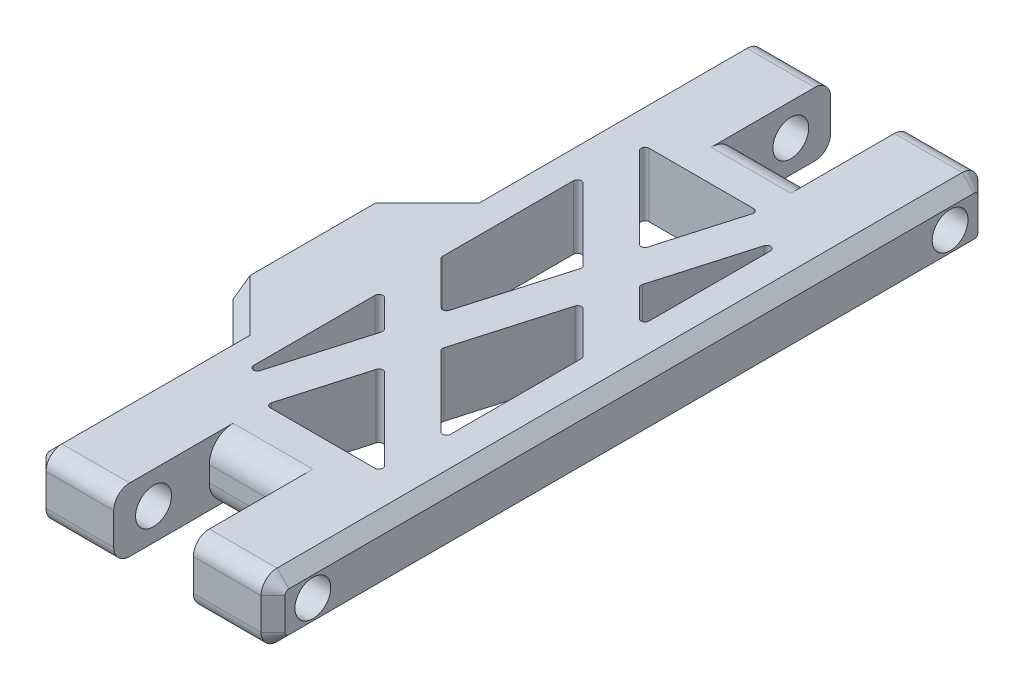
SolidWorks part; units mm, degrees
ref_plane "Front Plane" through (0, 0, 0) normal (0, 0, 1) x (1, 0, 0)
ref_plane "Top Plane" through (0, 0, 0) normal (0, 1, 0) x (1, 0, 0)
ref_plane "Right Plane" through (0, 0, 0) normal (1, 0, 0) x (0, 0, -1)
sketch "Sketch1" plane through (0, 0, 0) normal (0, 1, 0) x (1, 0, 0)
  line L1 (-15, 45) -> (15, 45)
  line L2 (-15, 45) -> (-15, -45)
  line L3 (-15, -45) -> (15, -45)
  line L4 (15, 45) -> (15, -45)
  line L5 (-15, 45) -> (15, -45) construction
  line L6 (-15, -45) -> (15, 45) construction
  point P0 (0, 0)
  dimension "D1" = 30
  dimension "D2" = 90
extrude "Boss-Extrude1" add sketch "Sketch1" along normal blind 8
sketch "Sketch2" plane through (0, 8, 0) normal (0, 1, 0) x (1, 0, 0)
  line L0 (15, 45) -> (-15, 45) construction
  line L1 (-5, 45) -> (5, 45)
  line L2 (-5, 45) -> (-5, 33)
  line L3 (-5, 33) -> (5, 33)
  line L4 (5, 45) -> (5, 33)
  line L5 (-15, -45) -> (15, -45) construction
  line L6 (5, -45) -> (-5, -45)
  line L7 (5, -45) -> (5, -33)
  line L8 (5, -33) -> (-5, -33)
  line L9 (-5, -45) -> (-5, -33)
  line L10 (15, -45) -> (15, 45) construction
  dimension "D1" = 10
  dimension "D2" = 10
  dimension "D3" = 10
  dimension "D4" = 12
  dimension "D5" = 12
  dimension "D6" = 10
extrude "Cut-Extrude1" cut sketch "Sketch2" against normal blind 8
sketch "Sketch3" plane through (15, 0, 0) normal (1, 0, 0) x (0, 0, -1)
  line L0 (-45, 8) -> (-45, 0) construction
  line L1 (-45, 8) -> (45, 8) construction
  circle A0 centre (-40, 4) radius 2.25
  dimension "D1" = 4.5
  dimension "D2" = 5
  dimension "D3" = 4
extrude "Cut-Extrude2" cut sketch "Sketch3" against normal through all
mirror "Mirror1" about plane through (0, 0, 0) normal (0, 0, 1) of "Cut-Extrude2"
fillet "Fillet1" radius 2 8 edges at (10, 0, -45) (10, 8, -45) (-10, 8, -45) (-10, 0, -45) (-10, 8, 45) (-10, 0, 45) (10, 0, 45) (10, 8, 45)
sketch "Sketch4" plane through (0, 8, 0) normal (0, 1, 0) x (1, 0, 0)
  line L0 (5, 26) -> (-10, 26)
  line L1 (-10, 26) -> (1.6418, 14.3582)
  line L2 (10, 6) -> (10, 26)
  line L3 (-10, -6) -> (-10, -26)
  line L4 (-5, -26) -> (10, -26)
  line L5 (10, -26) -> (-1.6418, -14.3582)
  line L6 (15, -43) -> (15, 43) construction
  line L7 (-15, 43) -> (-15, -43) construction
  line L8 (-10, 18.9289) -> (-10, 1.0711)
  line L9 (-10, 1.0711) -> (-3.9393, -4.9896)
  line L10 (9.8408, -18.7697) -> (9.8408, -0.9118)
  line L11 (9.8408, -0.9118) -> (3.9393, 4.9896)
  line L12 (-5, 33) -> (5, 33) construction
  line L13 (5, -33) -> (-5, -33) construction
  line L14 (5, 26) -> (1.6418, 14.3582)
  line L15 (-5, -26) -> (-1.6418, -14.3582)
  line L16 (-0.0587, -8.8702) -> (3.9393, 4.9896)
  line L18 (5.5224, 10.4776) -> (10, 6)
  line L19 (0.0587, 8.8702) -> (-10, 18.9289)
  line L20 (-0.0587, -8.8702) -> (9.8408, -18.7697)
  line L21 (-5.5224, -10.4776) -> (-10, -6)
  line L22 (-5.5224, -10.4776) -> (-10, -26)
  line L23 (0.0587, 8.8702) -> (-3.9393, -4.9896)
  line L24 (5.5224, 10.4776) -> (10, 26)
  dimension "D1" = 5
  dimension "D2" = 5
  dimension "D3" = 5
  dimension "D4" = 45
  dimension "D5" = 45
  dimension "D6" = 5
  dimension "D7" = 5
  dimension "D8" = 7
  dimension "D9" = 7
  dimension "D10" = 20
  dimension "D11" = 20
  dimension "D12" = 15
  dimension "D13" = 14
extrude "Cut-Extrude3" cut sketch "Sketch4" against normal through all
fillet "Fillet2" radius 3 4 edges at (0, 8, -33) (0, 8, 33) (0, 0, 33) (0, 0, -33)
sketch "Sketch5" plane through (-15, 0, 0) normal (-1, 0, 0) x (0, 0, 1)
  line L0 (-43, 0) -> (43, 0) construction
  line L1 (15, 0) -> (-5, 0)
  line L2 (15, 0) -> (15, 8)
  line L3 (15, 8) -> (-5, 8)
  line L4 (-5, 0) -> (-5, 8)
  line L5 (-43, 8) -> (43, 8) construction
  line L6 (-45, 6) -> (-45, 2) construction
  dimension "D1" = 40
  dimension "D2" = 20
extrude "Boss-Extrude2" add sketch "Sketch5" along normal blind 5
sketch "Sketch6" plane through (-20, 0, 0) normal (-1, 0, 0) x (0, 0, 1)
  line L0 (-5, 0) -> (15, 0) construction
  line L1 (-5, 8) -> (-5, 0) construction
  circle A0 centre (5, 4) radius 2
  dimension "D1" = 4
  dimension "D2" = 4
  dimension "D3" = 10
extrude "Cut-Extrude4" cut sketch "Sketch6" against normal blind 5
chamfer "Chamfer1" distance 5 angle 45 2 edges at (-15, 4, 15) (-15, 4, -5)
chamfer "Chamfer2" distance 1.5 angle 45 18 edges at (-15, 0, -26.5) (-15, 0.5858, -44.4142) (-15, 4, -45) (-15, 7.4142, -44.4142) (-15, 8, -26.5) (-15, 0, 31.5) (-15, 0.5858, 44.4142) (-15, 4, 45) (-15, 7.4142, 44.4142) (-15, 8, 31.5) (15, 0, 0) (15, 0.5858, 44.4142) (15, 0.5858, -44.4142) (15, 4, 45) (15, 4, -45) (15, 7.4142, 44.4142) (15, 7.4142, -44.4142) (15, 8, 0)
fillet "Fillet4" radius 0.5 20 edges at (10, 4, 26) (-1.6418, 4, 14.3582) (-5, 4, 26) (-5.5224, 4, 10.4776) (-10, 4, 6) (-10, 4, 26) (9.8408, 4, 18.7697) (9.8408, 4, 0.9118) (3.9393, 4, -4.9896) (-0.0587, 4, 8.8702) (-3.9393, 4, 4.9896) (-10, 4, -1.0711) (0.0587, 4, -8.8702) (-10, 4, -18.9289) (-10, 4, -26) (5.5224, 4, -10.4776) (10, 4, -6) (10, 4, -26) (1.6418, 4, -14.3582) (5, 4, -26)
chamfer "Chamfer3" distance 1.5 angle 45 4 edges at (-16.75, 0, 18.25) (-16.75, 8, 18.25) (-16.75, 8, -8.25) (-16.75, 0, -8.25)
